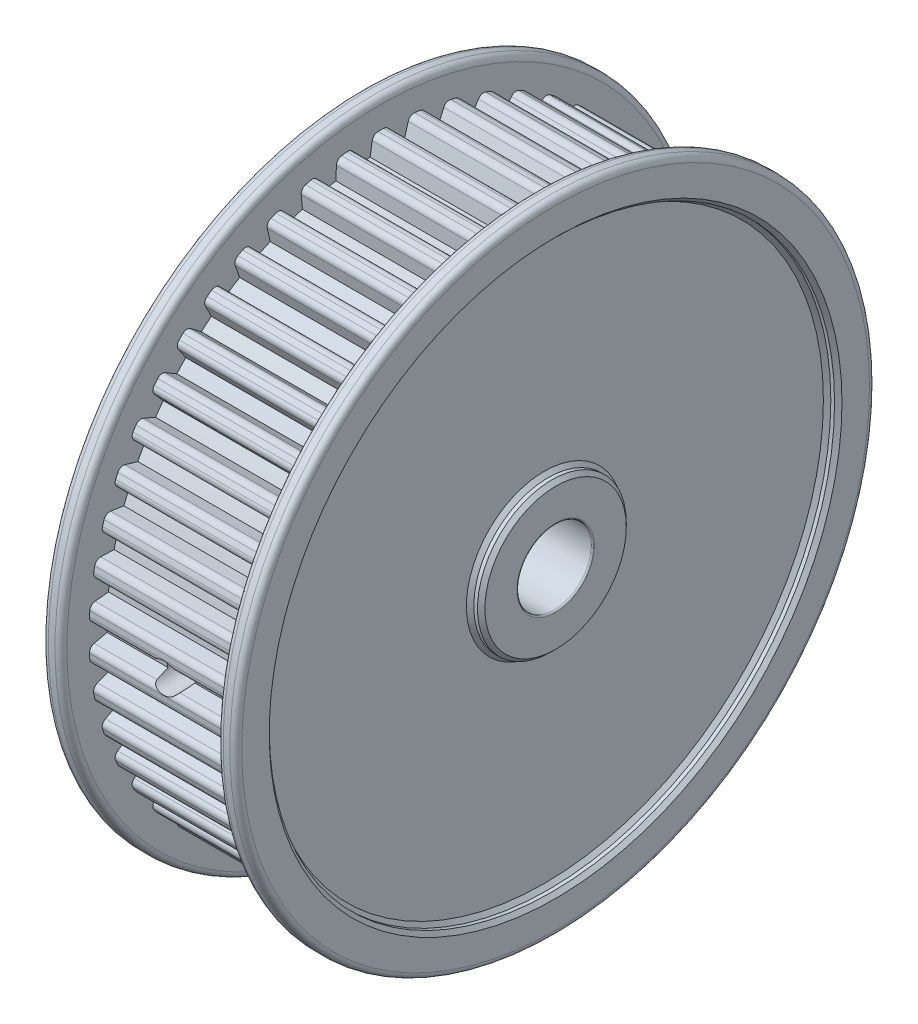
SolidWorks part; units mm, degrees
ref_plane "前视基准面" through (0, 0, 0) normal (0, 0, 1) x (1, 0, 0)
ref_plane "上视基准面" through (0, 0, 0) normal (0, 1, 0) x (1, 0, 0)
ref_plane "右视基准面" through (0, 0, 0) normal (1, 0, 0) x (0, 0, -1)
sketch "草图1" plane through (0, 0, 0) normal (1, 0, 0) x (0, 0, -1)
  circle A0 centre (0, 0) radius 43
  dimension "D1" = 86
extrude "凸台-拉伸1" add sketch "草图1" along normal blind 2.5
sketch "草图2" plane through (2.5, 0, 0) normal (1, 0, 0) x (0, 0, -1)
  line L0 (0, 0) -> (0, 45.6704) construction
  line L1 (1.1476, 38.5455) -> (1.4332, 36.7721)
  line L2 (-1.1476, 38.5455) -> (-1.4332, 36.7721)
  line L3 (3.6925, 38.3854) -> (3.1868, 36.6618)
  line L4 (5.9696, 38.0978) -> (6.0307, 36.3025)
  line L5 (8.4744, 37.62) -> (7.7566, 35.9732)
  line L6 (10.6974, 37.0492) -> (10.5331, 35.2604)
  line L7 (13.1226, 36.2612) -> (12.2041, 34.7174)
  line L8 (15.2566, 35.4163) -> (14.8693, 33.6622)
  line L9 (17.5638, 34.3306) -> (16.4591, 32.9141)
  line L10 (19.5751, 33.2249) -> (18.971, 31.5331)
  line L11 (21.7281, 31.8585) -> (20.4546, 30.5917)
  line L12 (23.5849, 30.5095) -> (22.7736, 28.9068)
  line L13 (25.5497, 28.8841) -> (24.1274, 27.7868)
  line L14 (27.2228, 27.3129) -> (26.217, 25.8246)
  line L15 (28.9684, 25.4541) -> (27.4198, 24.5437)
  line L16 (30.4314, 23.6856) -> (29.247, 22.3351)
  line L17 (31.9302, 21.6227) -> (30.2797, 20.9136)
  line L18 (33.16, 19.6848) -> (31.8157, 18.4933)
  line L19 (34.3884, 17.4503) -> (32.6621, 16.9536)
  line L20 (35.3657, 15.3735) -> (33.8826, 14.36)
  line L21 (36.3044, 13.0027) -> (34.5294, 12.7263)
  line L22 (37.0136, 10.8198) -> (35.4152, 10.0001)
  line L23 (37.6478, 8.35) -> (35.8522, 8.2983)
  line L24 (38.0778, 6.0955) -> (36.3893, 5.4825)
  line L25 (38.3974, 3.5656) -> (36.6095, 3.7394)
  line L26 (38.5415, 1.275) -> (36.7895, 0.8785)
  line L27 (38.5415, -1.275) -> (36.7895, -0.8785)
  line L28 (38.3974, -3.5656) -> (36.6095, -3.7394)
  line L29 (38.0778, -6.0955) -> (36.3893, -5.4825)
  line L30 (37.6478, -8.35) -> (35.8522, -8.2983)
  line L31 (37.0136, -10.8198) -> (35.4152, -10.0001)
  line L32 (36.3044, -13.0027) -> (34.5294, -12.7263)
  line L33 (35.3657, -15.3735) -> (33.8826, -14.36)
  line L34 (34.3884, -17.4503) -> (32.6621, -16.9536)
  line L35 (33.16, -19.6848) -> (31.8157, -18.4933)
  line L36 (31.9302, -21.6227) -> (30.2797, -20.9136)
  line L37 (30.4314, -23.6856) -> (29.247, -22.3351)
  line L38 (28.9684, -25.4541) -> (27.4198, -24.5437)
  line L39 (27.2228, -27.3129) -> (26.217, -25.8246)
  line L40 (25.5497, -28.8841) -> (24.1274, -27.7868)
  line L41 (23.5849, -30.5095) -> (22.7736, -28.9068)
  line L42 (21.7281, -31.8585) -> (20.4546, -30.5917)
  line L43 (19.5751, -33.2249) -> (18.971, -31.5331)
  line L44 (17.5638, -34.3306) -> (16.4591, -32.9141)
  line L45 (15.2566, -35.4163) -> (14.8693, -33.6622)
  line L46 (13.1226, -36.2612) -> (12.2041, -34.7174)
  line L47 (10.6974, -37.0492) -> (10.5331, -35.2604)
  line L48 (8.4744, -37.62) -> (7.7566, -35.9732)
  line L49 (5.9696, -38.0978) -> (6.0307, -36.3025)
  line L50 (3.6925, -38.3854) -> (3.1868, -36.6618)
  line L51 (1.1476, -38.5455) -> (1.4332, -36.7721)
  line L52 (-1.1476, -38.5455) -> (-1.4332, -36.7721)
  line L53 (-3.6925, -38.3854) -> (-3.1868, -36.6618)
  line L54 (-5.9696, -38.0978) -> (-6.0307, -36.3025)
  line L55 (-8.4744, -37.62) -> (-7.7566, -35.9732)
  line L56 (-10.6974, -37.0492) -> (-10.5331, -35.2604)
  line L57 (-13.1226, -36.2612) -> (-12.2041, -34.7174)
  line L58 (-15.2566, -35.4163) -> (-14.8693, -33.6622)
  line L59 (-17.5638, -34.3306) -> (-16.4591, -32.9141)
  line L60 (-19.5751, -33.2249) -> (-18.971, -31.5331)
  line L61 (-21.7281, -31.8585) -> (-20.4546, -30.5917)
  line L62 (-23.5849, -30.5095) -> (-22.7736, -28.9068)
  line L63 (-25.5497, -28.8841) -> (-24.1274, -27.7868)
  line L64 (-27.2228, -27.3129) -> (-26.217, -25.8246)
  line L65 (-28.9684, -25.4541) -> (-27.4198, -24.5437)
  line L66 (-30.4314, -23.6856) -> (-29.247, -22.3351)
  line L67 (-31.9302, -21.6227) -> (-30.2797, -20.9136)
  line L68 (-33.16, -19.6848) -> (-31.8157, -18.4933)
  line L69 (-34.3884, -17.4503) -> (-32.6621, -16.9536)
  line L70 (-35.3657, -15.3735) -> (-33.8826, -14.36)
  line L71 (-36.3044, -13.0027) -> (-34.5294, -12.7263)
  line L72 (-37.0136, -10.8198) -> (-35.4152, -10.0001)
  line L73 (-37.6478, -8.35) -> (-35.8522, -8.2983)
  line L74 (-38.0778, -6.0955) -> (-36.3893, -5.4825)
  line L75 (-38.3974, -3.5656) -> (-36.6095, -3.7394)
  line L76 (-38.5415, -1.275) -> (-36.7895, -0.8785)
  line L77 (-38.5415, 1.275) -> (-36.7895, 0.8785)
  line L78 (-38.3974, 3.5656) -> (-36.6095, 3.7394)
  line L79 (-38.0778, 6.0955) -> (-36.3893, 5.4825)
  line L80 (-37.6478, 8.35) -> (-35.8522, 8.2983)
  line L81 (-37.0136, 10.8198) -> (-35.4152, 10.0001)
  line L82 (-36.3044, 13.0027) -> (-34.5294, 12.7263)
  line L83 (-35.3657, 15.3735) -> (-33.8826, 14.36)
  line L84 (-34.3884, 17.4503) -> (-32.6621, 16.9536)
  line L85 (-33.16, 19.6848) -> (-31.8157, 18.4933)
  line L86 (-31.9302, 21.6227) -> (-30.2797, 20.9136)
  line L87 (-30.4314, 23.6856) -> (-29.247, 22.3351)
  line L88 (-28.9684, 25.4541) -> (-27.4198, 24.5437)
  line L89 (-27.2228, 27.3129) -> (-26.217, 25.8246)
  line L90 (-25.5497, 28.8841) -> (-24.1274, 27.7868)
  line L91 (-23.5849, 30.5095) -> (-22.7736, 28.9068)
  line L92 (-21.7281, 31.8585) -> (-20.4546, 30.5917)
  line L93 (-19.5751, 33.2249) -> (-18.971, 31.5331)
  line L94 (-17.5638, 34.3306) -> (-16.4591, 32.9141)
  line L95 (-15.2566, 35.4163) -> (-14.8693, 33.6622)
  line L96 (-13.1226, 36.2612) -> (-12.2041, 34.7174)
  line L97 (-10.6974, 37.0492) -> (-10.5331, 35.2604)
  line L98 (-8.4744, 37.62) -> (-7.7566, 35.9732)
  line L99 (-5.9696, 38.0978) -> (-6.0307, 36.3025)
  line L100 (-3.6925, 38.3854) -> (-3.1868, 36.6618)
  arc A0 (0.3652, 39.2183) -> (-0.3652, 39.2183) centre (0, 0) ccw
  arc A1 (-1.4332, 36.7721) -> (-3.1868, 36.6618) centre (0, 0) ccw
  arc A2 (1.1476, 38.5455) -> (0.3652, 39.2183) centre (0.3578, 38.4183) ccw
  arc A3 (-1.1476, 38.5455) -> (-0.3652, 39.2183) centre (-0.3578, 38.4183) cw
  arc A4 (3.6925, 38.3854) -> (4.553, 38.9548) centre (4.4601, 38.1602) cw
  arc A5 (5.9696, 38.0978) -> (5.2777, 38.8633) centre (5.17, 38.0706) ccw
  arc A6 (5.2777, 38.8633) -> (4.553, 38.9548) centre (0, 0) ccw
  arc A7 (8.4744, 37.62) -> (9.3994, 38.077) centre (9.2077, 37.3003) cw
  arc A8 (10.6974, 37.0492) -> (10.1069, 37.8954) centre (9.9008, 37.1224) ccw
  arc A9 (10.1069, 37.8954) -> (9.3994, 38.077) centre (0, 0) ccw
  arc A10 (13.1226, 36.2612) -> (14.0976, 36.5987) centre (13.8101, 35.8522) cw
  arc A11 (15.2566, 35.4163) -> (14.7768, 36.3298) centre (14.4754, 35.5888) ccw
  arc A12 (14.7768, 36.3298) -> (14.0976, 36.5987) centre (0, 0) ccw
  arc A13 (17.5638, 34.3306) -> (18.5735, 34.5432) centre (18.1947, 33.8386) cw
  arc A14 (19.5751, 33.2249) -> (19.2136, 34.1913) centre (18.8217, 33.4939) ccw
  arc A15 (19.2136, 34.1913) -> (18.5735, 34.5432) centre (0, 0) ccw
  arc A16 (21.7281, 31.8585) -> (22.7565, 31.9429) centre (22.2923, 31.2914) cw
  arc A17 (23.5849, 30.5095) -> (23.3474, 31.5136) centre (22.8712, 30.8708) ccw
  arc A18 (23.3474, 31.5136) -> (22.7565, 31.9429) centre (0, 0) ccw
  arc A19 (25.5497, 28.8841) -> (26.5805, 28.8389) centre (26.0384, 28.2507) cw
  arc A20 (27.2228, 27.3129) -> (27.113, 28.3389) centre (26.56, 27.7609) ccw
  arc A21 (27.113, 28.3389) -> (26.5805, 28.8389) centre (0, 0) ccw
  arc A22 (28.9684, 25.4541) -> (29.9854, 25.2801) centre (29.3738, 24.7644) cw
  arc A23 (30.4314, 23.6856) -> (30.451, 24.7173) centre (29.8299, 24.2131) ccw
  arc A24 (30.451, 24.7173) -> (29.9854, 25.2801) centre (0, 0) ccw
  arc A25 (31.9302, 21.6227) -> (32.9174, 21.3226) centre (32.246, 20.8876) cw
  arc A26 (33.16, 19.6848) -> (33.3088, 20.7059) centre (32.6294, 20.2835) ccw
  arc A27 (33.3088, 20.7059) -> (32.9174, 21.3226) centre (0, 0) ccw
  arc A28 (34.3884, 17.4503) -> (35.3303, 17.0288) centre (34.6096, 16.6815) cw
  arc A29 (35.3657, 15.3735) -> (35.6413, 16.3679) centre (34.9143, 16.034) ccw
  arc A30 (35.6413, 16.3679) -> (35.3303, 17.0288) centre (0, 0) ccw
  arc A31 (36.3044, 13.0027) -> (37.186, 12.4665) centre (36.4275, 12.2122) cw
  arc A32 (37.0136, 10.8198) -> (37.4117, 11.7718) centre (36.6486, 11.5317) ccw
  arc A33 (37.4117, 11.7718) -> (37.186, 12.4665) centre (0, 0) ccw
  arc A34 (37.6478, 8.35) -> (38.4552, 7.7075) centre (37.6708, 7.5503) cw
  arc A35 (38.0778, 6.0955) -> (38.5921, 6.99) centre (37.8049, 6.8474) ccw
  arc A36 (38.5921, 6.99) -> (38.4552, 7.7075) centre (0, 0) ccw
  arc A37 (38.3974, 3.5656) -> (39.118, 2.827) centre (38.3201, 2.7694) cw
  arc A38 (38.5415, 1.275) -> (39.1638, 2.098) centre (38.365, 2.0552) ccw
  arc A39 (39.1638, 2.098) -> (39.118, 2.827) centre (0, 0) ccw
  arc A40 (38.5415, -1.275) -> (39.1638, -2.098) centre (38.365, -2.0552) cw
  arc A41 (38.3974, -3.5656) -> (39.118, -2.827) centre (38.3201, -2.7694) ccw
  arc A42 (39.118, -2.827) -> (39.1638, -2.098) centre (0, 0) ccw
  arc A43 (38.0778, -6.0955) -> (38.5921, -6.99) centre (37.8049, -6.8474) cw
  arc A44 (37.6478, -8.35) -> (38.4552, -7.7075) centre (37.6708, -7.5503) ccw
  arc A45 (38.4552, -7.7075) -> (38.5921, -6.99) centre (0, 0) ccw
  arc A46 (37.0136, -10.8198) -> (37.4117, -11.7718) centre (36.6486, -11.5317) cw
  arc A47 (36.3044, -13.0027) -> (37.186, -12.4665) centre (36.4275, -12.2122) ccw
  arc A48 (37.186, -12.4665) -> (37.4117, -11.7718) centre (0, 0) ccw
  arc A49 (35.3657, -15.3735) -> (35.6413, -16.3679) centre (34.9143, -16.034) cw
  arc A50 (34.3884, -17.4503) -> (35.3303, -17.0288) centre (34.6096, -16.6815) ccw
  arc A51 (35.3303, -17.0288) -> (35.6413, -16.3679) centre (0, 0) ccw
  arc A52 (33.16, -19.6848) -> (33.3088, -20.7059) centre (32.6294, -20.2835) cw
  arc A53 (31.9302, -21.6227) -> (32.9174, -21.3226) centre (32.246, -20.8876) ccw
  arc A54 (32.9174, -21.3226) -> (33.3088, -20.7059) centre (0, 0) ccw
  arc A55 (30.4314, -23.6856) -> (30.451, -24.7173) centre (29.8299, -24.2131) cw
  arc A56 (28.9684, -25.4541) -> (29.9854, -25.2801) centre (29.3738, -24.7644) ccw
  arc A57 (29.9854, -25.2801) -> (30.451, -24.7173) centre (0, 0) ccw
  arc A58 (27.2228, -27.3129) -> (27.113, -28.3389) centre (26.56, -27.7609) cw
  arc A59 (25.5497, -28.8841) -> (26.5805, -28.8389) centre (26.0384, -28.2507) ccw
  arc A60 (26.5805, -28.8389) -> (27.113, -28.3389) centre (0, 0) ccw
  arc A61 (23.5849, -30.5095) -> (23.3474, -31.5136) centre (22.8712, -30.8708) cw
  arc A62 (21.7281, -31.8585) -> (22.7565, -31.9429) centre (22.2923, -31.2914) ccw
  arc A63 (22.7565, -31.9429) -> (23.3474, -31.5136) centre (0, 0) ccw
  arc A64 (19.5751, -33.2249) -> (19.2136, -34.1913) centre (18.8217, -33.4939) cw
  arc A65 (17.5638, -34.3306) -> (18.5735, -34.5432) centre (18.1947, -33.8386) ccw
  arc A66 (18.5735, -34.5432) -> (19.2136, -34.1913) centre (0, 0) ccw
  arc A67 (15.2566, -35.4163) -> (14.7768, -36.3298) centre (14.4754, -35.5888) cw
  arc A68 (13.1226, -36.2612) -> (14.0976, -36.5987) centre (13.8101, -35.8522) ccw
  arc A69 (14.0976, -36.5987) -> (14.7768, -36.3298) centre (0, 0) ccw
  arc A70 (10.6974, -37.0492) -> (10.1069, -37.8954) centre (9.9008, -37.1224) cw
  arc A71 (8.4744, -37.62) -> (9.3994, -38.077) centre (9.2077, -37.3003) ccw
  arc A72 (9.3994, -38.077) -> (10.1069, -37.8954) centre (0, 0) ccw
  arc A73 (5.9696, -38.0978) -> (5.2777, -38.8633) centre (5.17, -38.0706) cw
  arc A74 (3.6925, -38.3854) -> (4.553, -38.9548) centre (4.4601, -38.1602) ccw
  arc A75 (4.553, -38.9548) -> (5.2777, -38.8633) centre (0, 0) ccw
  arc A76 (1.1476, -38.5455) -> (0.3652, -39.2183) centre (0.3578, -38.4183) cw
  arc A77 (-1.1476, -38.5455) -> (-0.3652, -39.2183) centre (-0.3578, -38.4183) ccw
  arc A78 (-0.3652, -39.2183) -> (0.3652, -39.2183) centre (0, 0) ccw
  arc A79 (-3.6925, -38.3854) -> (-4.553, -38.9548) centre (-4.4601, -38.1602) cw
  arc A80 (-5.9696, -38.0978) -> (-5.2777, -38.8633) centre (-5.17, -38.0706) ccw
  arc A81 (-5.2777, -38.8633) -> (-4.553, -38.9548) centre (0, 0) ccw
  arc A82 (-8.4744, -37.62) -> (-9.3994, -38.077) centre (-9.2077, -37.3003) cw
  arc A83 (-10.6974, -37.0492) -> (-10.1069, -37.8954) centre (-9.9008, -37.1224) ccw
  arc A84 (-10.1069, -37.8954) -> (-9.3994, -38.077) centre (0, 0) ccw
  arc A85 (-13.1226, -36.2612) -> (-14.0976, -36.5987) centre (-13.8101, -35.8522) cw
  arc A86 (-15.2566, -35.4163) -> (-14.7768, -36.3298) centre (-14.4754, -35.5888) ccw
  arc A87 (-14.7768, -36.3298) -> (-14.0976, -36.5987) centre (0, 0) ccw
  arc A88 (-17.5638, -34.3306) -> (-18.5735, -34.5432) centre (-18.1947, -33.8386) cw
  arc A89 (-19.5751, -33.2249) -> (-19.2136, -34.1913) centre (-18.8217, -33.4939) ccw
  arc A90 (-19.2136, -34.1913) -> (-18.5735, -34.5432) centre (0, 0) ccw
  arc A91 (-21.7281, -31.8585) -> (-22.7565, -31.9429) centre (-22.2923, -31.2914) cw
  arc A92 (-23.5849, -30.5095) -> (-23.3474, -31.5136) centre (-22.8712, -30.8708) ccw
  arc A93 (-23.3474, -31.5136) -> (-22.7565, -31.9429) centre (0, 0) ccw
  arc A94 (-25.5497, -28.8841) -> (-26.5805, -28.8389) centre (-26.0384, -28.2507) cw
  arc A95 (-27.2228, -27.3129) -> (-27.113, -28.3389) centre (-26.56, -27.7609) ccw
  arc A96 (-27.113, -28.3389) -> (-26.5805, -28.8389) centre (0, 0) ccw
  arc A97 (-28.9684, -25.4541) -> (-29.9854, -25.2801) centre (-29.3738, -24.7644) cw
  arc A98 (-30.4314, -23.6856) -> (-30.451, -24.7173) centre (-29.8299, -24.2131) ccw
  arc A99 (-30.451, -24.7173) -> (-29.9854, -25.2801) centre (0, 0) ccw
  arc A100 (-31.9302, -21.6227) -> (-32.9174, -21.3226) centre (-32.246, -20.8876) cw
  arc A101 (-33.16, -19.6848) -> (-33.3088, -20.7059) centre (-32.6294, -20.2835) ccw
  arc A102 (-33.3088, -20.7059) -> (-32.9174, -21.3226) centre (0, 0) ccw
  arc A103 (-34.3884, -17.4503) -> (-35.3303, -17.0288) centre (-34.6096, -16.6815) cw
  arc A104 (-35.3657, -15.3735) -> (-35.6413, -16.3679) centre (-34.9143, -16.034) ccw
  arc A105 (-35.6413, -16.3679) -> (-35.3303, -17.0288) centre (0, 0) ccw
  arc A106 (-36.3044, -13.0027) -> (-37.186, -12.4665) centre (-36.4275, -12.2122) cw
  arc A107 (-37.0136, -10.8198) -> (-37.4117, -11.7718) centre (-36.6486, -11.5317) ccw
  arc A108 (-37.4117, -11.7718) -> (-37.186, -12.4665) centre (0, 0) ccw
  arc A109 (-37.6478, -8.35) -> (-38.4552, -7.7075) centre (-37.6708, -7.5503) cw
  arc A110 (-38.0778, -6.0955) -> (-38.5921, -6.99) centre (-37.8049, -6.8474) ccw
  arc A111 (-38.5921, -6.99) -> (-38.4552, -7.7075) centre (0, 0) ccw
  arc A112 (-38.3974, -3.5656) -> (-39.118, -2.827) centre (-38.3201, -2.7694) cw
  arc A113 (-38.5415, -1.275) -> (-39.1638, -2.098) centre (-38.365, -2.0552) ccw
  arc A114 (-39.1638, -2.098) -> (-39.118, -2.827) centre (0, 0) ccw
  arc A115 (-38.5415, 1.275) -> (-39.1638, 2.098) centre (-38.365, 2.0552) cw
  arc A116 (-38.3974, 3.5656) -> (-39.118, 2.827) centre (-38.3201, 2.7694) ccw
  arc A117 (-39.118, 2.827) -> (-39.1638, 2.098) centre (0, 0) ccw
  arc A118 (-38.0778, 6.0955) -> (-38.5921, 6.99) centre (-37.8049, 6.8474) cw
  arc A119 (-37.6478, 8.35) -> (-38.4552, 7.7075) centre (-37.6708, 7.5503) ccw
  arc A120 (-38.4552, 7.7075) -> (-38.5921, 6.99) centre (0, 0) ccw
  arc A121 (-37.0136, 10.8198) -> (-37.4117, 11.7718) centre (-36.6486, 11.5317) cw
  arc A122 (-36.3044, 13.0027) -> (-37.186, 12.4665) centre (-36.4275, 12.2122) ccw
  arc A123 (-37.186, 12.4665) -> (-37.4117, 11.7718) centre (0, 0) ccw
  arc A124 (-35.3657, 15.3735) -> (-35.6413, 16.3679) centre (-34.9143, 16.034) cw
  arc A125 (-34.3884, 17.4503) -> (-35.3303, 17.0288) centre (-34.6096, 16.6815) ccw
  arc A126 (-35.3303, 17.0288) -> (-35.6413, 16.3679) centre (0, 0) ccw
  arc A127 (-33.16, 19.6848) -> (-33.3088, 20.7059) centre (-32.6294, 20.2835) cw
  arc A128 (-31.9302, 21.6227) -> (-32.9174, 21.3226) centre (-32.246, 20.8876) ccw
  arc A129 (-32.9174, 21.3226) -> (-33.3088, 20.7059) centre (0, 0) ccw
  arc A130 (-30.4314, 23.6856) -> (-30.451, 24.7173) centre (-29.8299, 24.2131) cw
  arc A131 (-28.9684, 25.4541) -> (-29.9854, 25.2801) centre (-29.3738, 24.7644) ccw
  arc A132 (-29.9854, 25.2801) -> (-30.451, 24.7173) centre (0, 0) ccw
  arc A133 (-27.2228, 27.3129) -> (-27.113, 28.3389) centre (-26.56, 27.7609) cw
  arc A134 (-25.5497, 28.8841) -> (-26.5805, 28.8389) centre (-26.0384, 28.2507) ccw
  arc A135 (-26.5805, 28.8389) -> (-27.113, 28.3389) centre (0, 0) ccw
  arc A136 (-23.5849, 30.5095) -> (-23.3474, 31.5136) centre (-22.8712, 30.8708) cw
  arc A137 (-21.7281, 31.8585) -> (-22.7565, 31.9429) centre (-22.2923, 31.2914) ccw
  arc A138 (-22.7565, 31.9429) -> (-23.3474, 31.5136) centre (0, 0) ccw
  arc A139 (-19.5751, 33.2249) -> (-19.2136, 34.1913) centre (-18.8217, 33.4939) cw
  arc A140 (-17.5638, 34.3306) -> (-18.5735, 34.5432) centre (-18.1947, 33.8386) ccw
  arc A141 (-18.5735, 34.5432) -> (-19.2136, 34.1913) centre (0, 0) ccw
  arc A142 (-15.2566, 35.4163) -> (-14.7768, 36.3298) centre (-14.4754, 35.5888) cw
  arc A143 (-13.1226, 36.2612) -> (-14.0976, 36.5987) centre (-13.8101, 35.8522) ccw
  arc A144 (-14.0976, 36.5987) -> (-14.7768, 36.3298) centre (0, 0) ccw
  arc A145 (-10.6974, 37.0492) -> (-10.1069, 37.8954) centre (-9.9008, 37.1224) cw
  arc A146 (-8.4744, 37.62) -> (-9.3994, 38.077) centre (-9.2077, 37.3003) ccw
  arc A147 (-9.3994, 38.077) -> (-10.1069, 37.8954) centre (0, 0) ccw
  arc A148 (-5.9696, 38.0978) -> (-5.2777, 38.8633) centre (-5.17, 38.0706) cw
  arc A149 (-3.6925, 38.3854) -> (-4.553, 38.9548) centre (-4.4601, 38.1602) ccw
  arc A150 (-4.553, 38.9548) -> (-5.2777, 38.8633) centre (0, 0) ccw
  arc A151 (3.1868, 36.6618) -> (1.4332, 36.7721) centre (0, 0) ccw
  arc A152 (7.7566, 35.9732) -> (6.0307, 36.3025) centre (0, 0) ccw
  arc A153 (12.2041, 34.7174) -> (10.5331, 35.2604) centre (0, 0) ccw
  arc A154 (16.4591, 32.9141) -> (14.8693, 33.6622) centre (0, 0) ccw
  arc A155 (20.4546, 30.5917) -> (18.971, 31.5331) centre (0, 0) ccw
  arc A156 (24.1274, 27.7868) -> (22.7736, 28.9068) centre (0, 0) ccw
  arc A157 (27.4198, 24.5437) -> (26.217, 25.8246) centre (0, 0) ccw
  arc A158 (30.2797, 20.9136) -> (29.247, 22.3351) centre (0, 0) ccw
  arc A159 (32.6621, 16.9536) -> (31.8157, 18.4933) centre (0, 0) ccw
  arc A160 (34.5294, 12.7263) -> (33.8826, 14.36) centre (0, 0) ccw
  arc A161 (35.8522, 8.2983) -> (35.4152, 10.0001) centre (0, 0) ccw
  arc A162 (36.6095, 3.7394) -> (36.3893, 5.4825) centre (0, 0) ccw
  arc A163 (36.7895, -0.8785) -> (36.7895, 0.8785) centre (0, 0) ccw
  arc A164 (36.3893, -5.4825) -> (36.6095, -3.7394) centre (0, 0) ccw
  arc A165 (35.4152, -10.0001) -> (35.8522, -8.2983) centre (0, 0) ccw
  arc A166 (33.8826, -14.36) -> (34.5294, -12.7263) centre (0, 0) ccw
  arc A167 (31.8157, -18.4933) -> (32.6621, -16.9536) centre (0, 0) ccw
  arc A168 (29.247, -22.3351) -> (30.2797, -20.9136) centre (0, 0) ccw
  arc A169 (26.217, -25.8246) -> (27.4198, -24.5437) centre (0, 0) ccw
  arc A170 (22.7736, -28.9068) -> (24.1274, -27.7868) centre (0, 0) ccw
  arc A171 (18.971, -31.5331) -> (20.4546, -30.5917) centre (0, 0) ccw
  arc A172 (14.8693, -33.6622) -> (16.4591, -32.9141) centre (0, 0) ccw
  arc A173 (10.5331, -35.2604) -> (12.2041, -34.7174) centre (0, 0) ccw
  arc A174 (6.0307, -36.3025) -> (7.7566, -35.9732) centre (0, 0) ccw
  arc A175 (1.4332, -36.7721) -> (3.1868, -36.6618) centre (0, 0) ccw
  arc A176 (-3.1868, -36.6618) -> (-1.4332, -36.7721) centre (0, 0) ccw
  arc A177 (-7.7566, -35.9732) -> (-6.0307, -36.3025) centre (0, 0) ccw
  arc A178 (-12.2041, -34.7174) -> (-10.5331, -35.2604) centre (0, 0) ccw
  arc A179 (-16.4591, -32.9141) -> (-14.8693, -33.6622) centre (0, 0) ccw
  arc A180 (-20.4546, -30.5917) -> (-18.971, -31.5331) centre (0, 0) ccw
  arc A181 (-27.4198, -24.5437) -> (-26.217, -25.8246) centre (0, 0) ccw
  arc A182 (-24.1274, -27.7868) -> (-22.7736, -28.9068) centre (0, 0) ccw
  arc A183 (-30.2797, -20.9136) -> (-29.247, -22.3351) centre (0, 0) ccw
  arc A184 (-32.6621, -16.9536) -> (-31.8157, -18.4933) centre (0, 0) ccw
  arc A185 (-34.5294, -12.7263) -> (-33.8826, -14.36) centre (0, 0) ccw
  arc A186 (-35.8522, -8.2983) -> (-35.4152, -10.0001) centre (0, 0) ccw
  arc A187 (-36.6095, -3.7394) -> (-36.3893, -5.4825) centre (0, 0) ccw
  arc A188 (-36.7895, 0.8785) -> (-36.7895, -0.8785) centre (0, 0) ccw
  arc A189 (-35.4152, 10.0001) -> (-35.8522, 8.2983) centre (0, 0) ccw
  arc A190 (-36.3893, 5.4825) -> (-36.6095, 3.7394) centre (0, 0) ccw
  arc A191 (-33.8826, 14.36) -> (-34.5294, 12.7263) centre (0, 0) ccw
  arc A192 (-31.8157, 18.4933) -> (-32.6621, 16.9536) centre (0, 0) ccw
  arc A193 (-29.247, 22.3351) -> (-30.2797, 20.9136) centre (0, 0) ccw
  arc A194 (-26.217, 25.8246) -> (-27.4198, 24.5437) centre (0, 0) ccw
  arc A195 (-22.7736, 28.9068) -> (-24.1274, 27.7868) centre (0, 0) ccw
  arc A196 (-18.971, 31.5331) -> (-20.4546, 30.5917) centre (0, 0) ccw
  arc A197 (-14.8693, 33.6622) -> (-16.4591, 32.9141) centre (0, 0) ccw
  arc A198 (-10.5331, 35.2604) -> (-12.2041, 34.7174) centre (0, 0) ccw
  arc A199 (-6.0307, 36.3025) -> (-7.7566, 35.9732) centre (0, 0) ccw
  point P10 (1.0412, 39.2062)
  point P13 (-1.0412, 39.2062)
  point P409 (0, 0)
  dimension "D1" = 78.44
  dimension "D2" = 73.6
  dimension "D5" = 0.8
  dimension "D3" = 9.15
  dimension "D4" = 2.4341
  dimension "D6" = 50
extrude "凸台-拉伸2" add sketch "草图2" along normal blind 21
sketch "草图3" plane through (23.5, 0, 0) normal (1, 0, 0) x (0, 0, -1)
  circle A0 centre (0, 0) radius 43
  dimension "D1" = 86
extrude "凸台-拉伸3" add sketch "草图3" along normal blind 2.5
sketch "草图4" plane through (26, 0, 0) normal (1, 0, 0) x (0, 0, -1)
  circle A0 centre (0, 0) radius 5
  dimension "D1" = 10
extrude "切除-拉伸1" cut sketch "草图4" against normal through all
sketch "草图5" plane through (26, 0, 0) normal (1, 0, 0) x (0, 0, -1)
  circle A0 centre (0, 0) radius 10
  circle A1 centre (0, 0) radius 38
  dimension "D1" = 20
  dimension "D2" = 76
extrude "切除-拉伸2" cut sketch "草图5" against normal blind 1.5
sketch "草图6" plane through (0, 0, 0) normal (-1, 0, 0) x (0, 0, 1)
  circle A0 centre (0, 0) radius 10
  circle A1 centre (0, 0) radius 38
  dimension "D1" = 20
  dimension "D2" = 76
extrude "切除-拉伸3" cut sketch "草图6" against normal blind 1.5
fillet "圆角1" radius 0.8 4 edges at (26, 0, -43) (23.5, 0, -43) (2.5, 0, -43) (0, 0, -43)
chamfer "倒角1" distance 0.5 angle 45 4 edges at (0, 0, 10) (1.5, 0, 10) (1.5, 0, 38) (0, 0, 38)
chamfer "倒角2" distance 0.5 angle 45 4 edges at (24.5, 0, -10) (26, 0, -10) (24.5, 0, -38) (26, 0, -38)
fillet "圆角2" radius 0.2 2 edges at (0, 0, -5) (26, 0, -5)
sketch "草图7" plane through (0, 0, 0) normal (0, 0, 1) x (1, 0, 0)
  line L0 (0, 0) -> (12.5, 0) construction
  circle A0 centre (12.5, 0) radius 2
  dimension "D2" = 4
  dimension "D1" = 12.5
extrude "切除-拉伸4" cut sketch "草图7" against normal through all both and the other way through all
cosmetic thread "装饰螺纹线1" parameters "D2"=5
cosmetic thread "装饰螺纹线2" parameters "D2"=5
